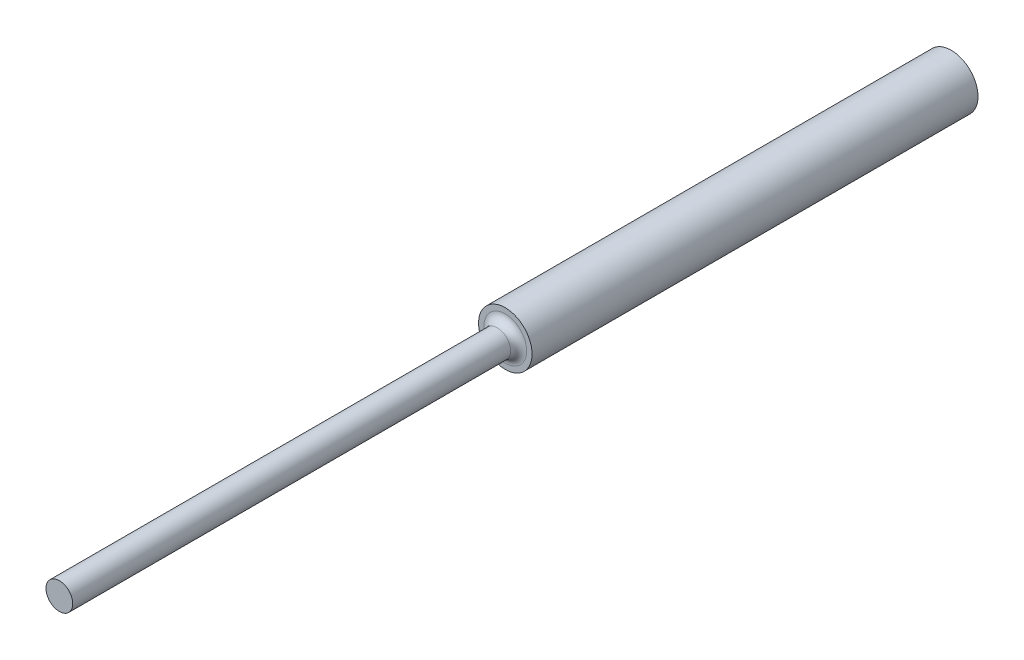
SolidWorks part; units mm, degrees
ref_plane "Front Plane" through (0, 0, 0) normal (0, 0, 1) x (1, 0, 0)
ref_plane "Top Plane" through (0, 0, 0) normal (0, 1, 0) x (1, 0, 0)
ref_plane "Right Plane" through (0, 0, 0) normal (1, 0, 0) x (0, 0, -1)
sketch "Sketch1" plane through (0, 0, 0) normal (0, 0, 1) x (1, 0, 0)
  circle A0 centre (0, 0) radius 30
extrude "Boss-Extrude1" add sketch "Sketch1" along normal blind 500 contours A0
sketch "Sketch2" plane through (0, 0, 500) normal (0, 0, 1) x (1, 0, 0)
  circle A0 centre (0, 0) radius 15
extrude "Boss-Extrude2" add sketch "Sketch2" along normal blind 500 contours A0
fillet "Fillet3" radius 9 1 edges at (15, 0, 500)
ref_axis "Axis1" through (0, 0, -50) along (0, 0, 1)
